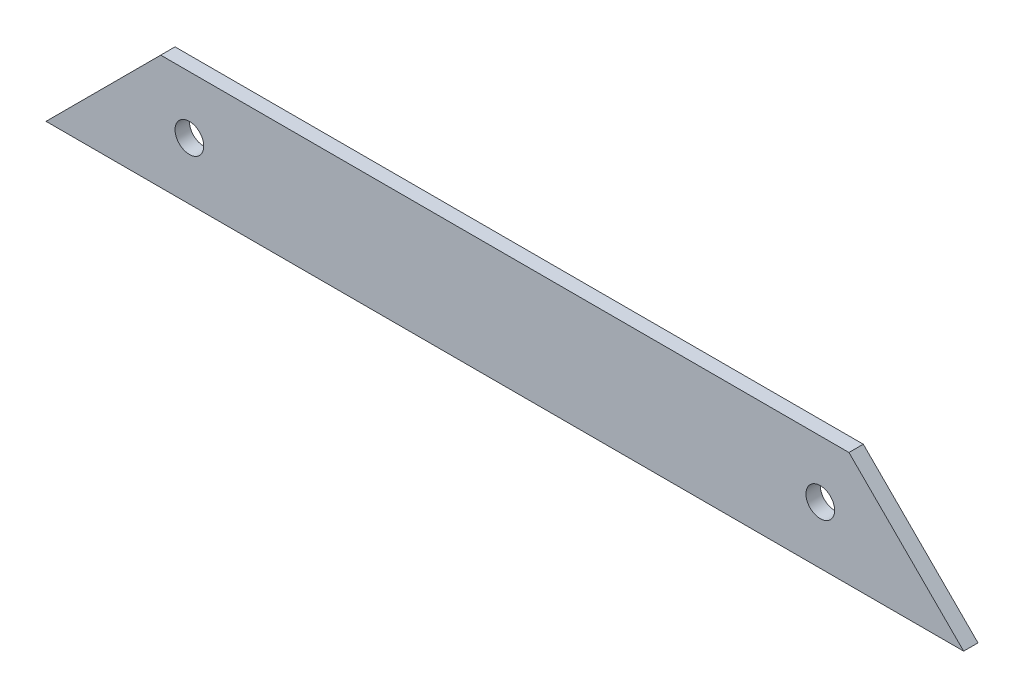
SolidWorks part; units mm, degrees
material "6061 Alloy"
ref_plane "Front Plane" through (0, 0, 0) normal (0, 0, 1) x (1, 0, 0)
ref_plane "Top Plane" through (0, 0, 0) normal (0, 1, 0) x (1, 0, 0)
ref_plane "Right Plane" through (0, 0, 0) normal (1, 0, 0) x (0, 0, -1)
ref_axis "Axis1" through (0, -67.7, 0) along (0, 1, 0)
sketch "Sketch3" plane through (0, 0, 0) normal (0, 0, 1) x (1, 0, 0)
  line L0 (76.2, 0) -> (-76.2, 0)
  line L1 (-76.2, 0) -> (-101.6, -25.4)
  line L2 (-101.6, -25.4) -> (101.6, -25.4)
  line L3 (0, -67.7) -> (0, 42.3) construction
  line L4 (0, 0) -> (0, -25.4) construction
  line L5 (76.2, 0) -> (101.6, -25.4)
  circle A0 centre (-69.85, -12.7) radius 3.175
  circle A1 centre (69.85, -12.7) radius 3.175
  dimension "D4" = 31.75
  dimension "D5" = 6.35
  dimension "D1" = 76.2
  dimension "D2" = 25.4
  dimension "D3" = 12.7
  dimension "D6" = 45
extrude "Boss-Extrude1" add sketch "Sketch3" along normal blind 3.175
